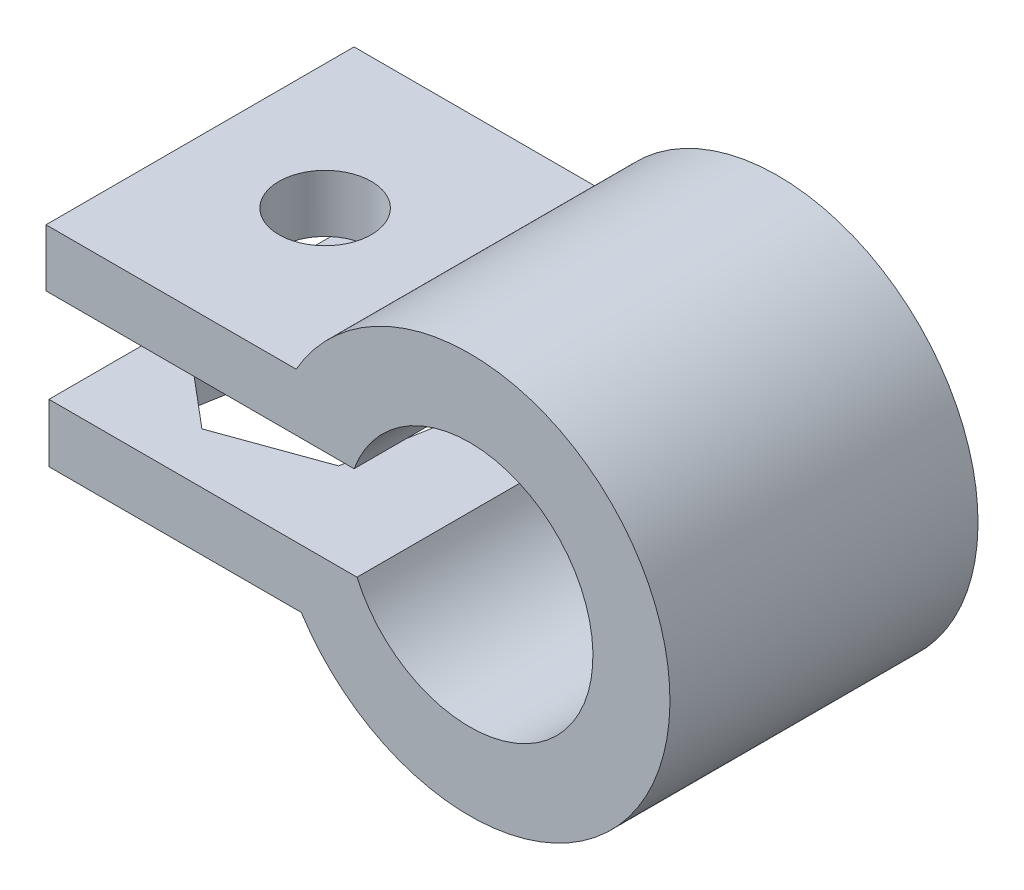
SolidWorks part; units mm, degrees
ref_plane "Front Plane" through (0, 0, 0) normal (0, 0, 1) x (1, 0, 0)
ref_plane "Top Plane" through (0, 0, 0) normal (0, 1, 0) x (1, 0, 0)
ref_plane "Right Plane" through (0, 0, 0) normal (1, 0, 0) x (0, 0, -1)
sketch "Sketch1" plane through (0, 0, 0) normal (0, 0, 1) x (1, 0, 0)
  circle A0 centre (-12.3154, 2.5507) radius 4
  circle A1 centre (-12.3154, 2.5507) radius 6.5
  dimension "D1" = 8
  dimension "D2" = 13
extrude "Boss-Extrude1" add sketch "Sketch1" along normal blind 10
sketch "Sketch2" plane through (0, 0, 10) normal (0, 0, 1) x (1, 0, 0)
  line L1 (-18.9664, 3.9327) -> (-15.7482, 3.9327)
  line L2 (-18.9664, 3.9327) -> (-18.9664, 0.9327)
  line L3 (-18.9664, 0.9327) -> (-15.7482, 0.9327)
  line L4 (-15.7482, 3.9327) -> (-15.7482, 0.9327)
  dimension "D1" = 3
extrude "Cut-Extrude1" cut sketch "Sketch2" against normal blind 33
sketch "Sketch3" plane through (0, 0, 10) normal (0, 0, 1) x (1, 0, 0)
  line L0 (-15.9736, 0.9327) -> (-25.9736, 0.9327)
  line L1 (-16.0691, 5.7921) -> (-26.0691, 5.7921)
  line L2 (-16.0691, 5.7921) -> (-16.0691, 3.9327)
  line L3 (-16.0691, 3.9327) -> (-26.0691, 3.9327)
  line L4 (-26.0691, 5.7921) -> (-26.0691, 3.9327)
  line L5 (-15.9736, 0.9327) -> (-15.9736, -0.9625)
  line L6 (-15.9736, -0.9625) -> (-25.9736, -0.9625)
  line L7 (-25.9736, 0.9327) -> (-25.9736, -0.9625)
  line L8 (-16.0691, 3.9327) -> (-18.6668, 3.9327) construction
  line L9 (-18.6108, 0.9327) -> (-15.9736, 0.9327) construction
  dimension "D1" = 10
  dimension "D2" = 0
  dimension "D3" = 0
  dimension "D4" = 0
  dimension "D5" = 0
  dimension "D6" = 10
extrude "Boss-Extrude2" add sketch "Sketch3" against normal blind 10 contours L2 L1 L4 L3 | L0 L7 L6 L5
sketch "Sketch4" plane through (0, 5.7921, 0) normal (0, 1, 0) x (1, 0, 0)
  line L0 (-17.9496, 0) -> (-26.0691, 0) construction
  line L1 (-26.0691, 0) -> (-26.0691, -10) construction
  circle A0 centre (-22.0091, -5) radius 1.5
  dimension "D1" = 5
  dimension "D2" = 4.06
  dimension "D3" = 3
extrude "Cut-Extrude2" cut sketch "Sketch4" against normal blind 40
sketch "Sketch5" plane through (0, -0.9625, 0) normal (0, -1, 0) x (-1, 0, 0)
  line L1 (19.403, -7.1706) -> (22.661, -8.3474)
  line L2 (22.661, -8.3474) -> (25.3092, -6.1142)
  line L3 (25.3092, -6.1142) -> (24.6993, -2.7042)
  line L4 (24.6993, -2.7042) -> (21.4413, -1.5274)
  line L5 (21.4413, -1.5274) -> (18.7931, -3.7606)
  line L6 (18.7931, -3.7606) -> (19.403, -7.1706)
  circle A0 centre (22.0511, -4.9374) radius 3 construction
  dimension "D1" = 6
extrude "Cut-Extrude3" cut sketch "Sketch5" against normal blind 3
